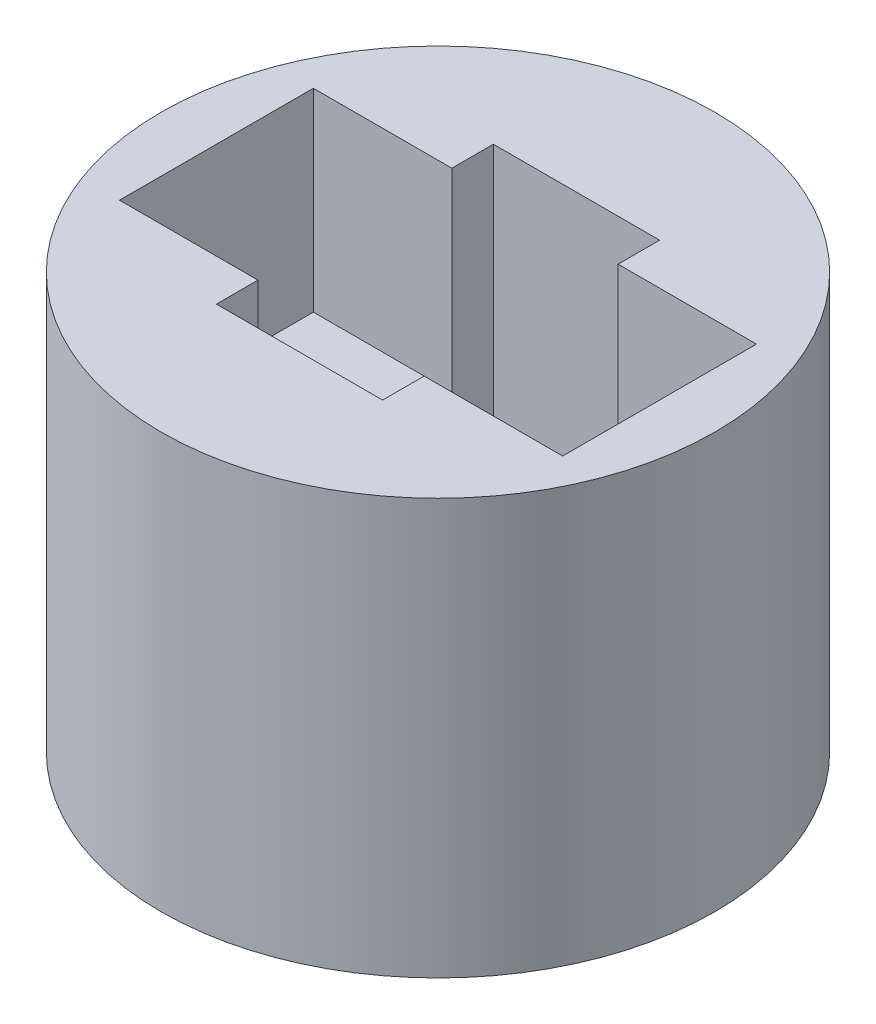
SolidWorks part; units mm, degrees
ref_plane "Alzado" through (0, 0, 0) normal (0, 0, 1) x (1, 0, 0)
ref_plane "Planta" through (0, 0, 0) normal (0, 1, 0) x (1, 0, 0)
ref_plane "Vista lateral" through (0, 0, 0) normal (1, 0, 0) x (0, 0, -1)
sketch "Croquis1" plane through (0, 0, 0) normal (0, 0, 1) x (1, 0, 0)
  line L1 (0, 0) -> (5, 0)
  line L2 (0, 0) -> (0, 7.5)
  line L3 (0, 7.5) -> (5, 7.5)
  line L4 (5, 0) -> (5, 7.5)
  dimension "D1" = 5
  dimension "D2" = 7.5
revolve "Revolución1" add sketch "Croquis1" angle 360 about L2
sketch "Croquis2" plane through (0, 7.5, 0) normal (0, 1, 0) x (1, 0, 0)
  line L0 (-2.5, 0.5) -> (2.5, 0.5)
  line L1 (-1.5, -2.5) -> (1.5, -2.5)
  line L2 (-1.5, -2.5) -> (-1.5, 2.5)
  line L3 (-1.5, 2.5) -> (1.5, 2.5)
  line L4 (1.5, -2.5) -> (1.5, 2.5)
  line L5 (-1.5, -2.5) -> (1.5, 2.5) construction
  line L6 (-1.5, 2.5) -> (1.5, -2.5) construction
  line L7 (-2.5, -0.5) -> (2.5, -0.5)
  circle A0 centre (2.5, 0) radius 0.5
  circle A1 centre (-2.5, 0) radius 0.5
  point P0 (0, 0)
  point P13 (0, 0)
  dimension "D3" = 1
  dimension "D1" = 3
  dimension "D2" = 5
  dimension "D4" = 2.5
  dimension "D5" = 2
extrude "Cortar-Extruir1" cut sketch "Croquis2" against normal through all contours A1 | A1 L7 L2 L0 | L2 L7 L4 L0 | L0 L4 L3 L2 | L7 L2 L1 L4 | A0 L0 L4 L7 | A0 region at (-1.8139, 7.5, 0) region at (-2.5, 7.5, 0) region at (0, 7.5, -1.5) region at (0, 7.5, 0) region at (1.8139, 7.5, 0) region at (0, 7.5, 1.5) region at (2.5, 7.5, 0)
sketch "Croquis3" plane through (0, 7.5, 0) normal (0, 1, 0) x (1, 0, 0)
  line L1 (-4, -1.75) -> (4, -1.75)
  line L2 (-4, -1.75) -> (-4, 1.75)
  line L3 (-4, 1.75) -> (4, 1.75)
  line L4 (4, -1.75) -> (4, 1.75)
  line L5 (-4, -1.75) -> (4, 1.75) construction
  line L6 (-4, 1.75) -> (4, -1.75) construction
  point P0 (0, 0)
  dimension "D1" = 8
  dimension "D2" = 3.5
extrude "Cortar-Extruir2" cut sketch "Croquis3" against normal blind 3.5
